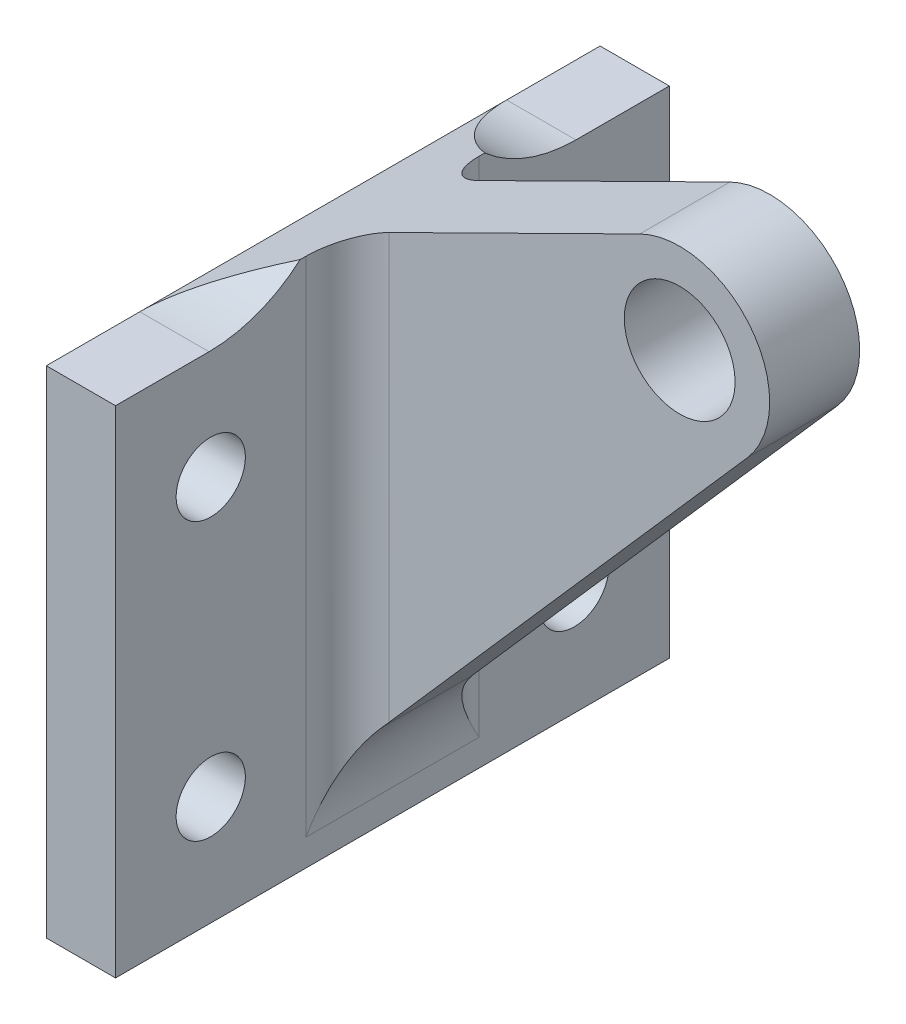
SolidWorks part; units mm, degrees
ref_plane "Front Plane" through (0, 0, 0) normal (0, 0, 1) x (1, 0, 0)
ref_plane "Top Plane" through (0, 0, 0) normal (0, 1, 0) x (1, 0, 0)
ref_plane "Right Plane" through (0, 0, 0) normal (1, 0, 0) x (0, 0, -1)
sketch "Sketch1" plane through (0, 0, 0) normal (0, 0, 1) x (1, 0, 0)
  line L0 (0, 0) -> (39, 35) construction
  line L1 (39, 35) -> (39, 0) construction
  line L2 (39, 0) -> (0, 0) construction
  line L3 (0, 0) -> (0, 20) construction
  line L4 (0, 20) -> (39, 35) construction
  line L5 (10, 0) -> (10, -7.9) construction
  line L6 (0, 20) -> (10, 20) construction
  line L7 (10, 20) -> (10, 27.9) construction
  line L8 (10, 27.9) -> (10, -7.9)
  line L9 (10, 27.9) -> (36.1168, 40.8256)
  line L10 (10, -7.9) -> (43.8855, 30.7126)
  circle A0 centre (39, 35) radius 6.5 construction
  circle A1 centre (39, 35) radius 6.5
  circle A2 centre (39, 35) radius 4
  point P3 (10, 0)
  dimension "D5" = 13
  dimension "D9" = 8
  dimension "D1" = 20
  dimension "D2" = 10
  dimension "D3" = 39
  dimension "D4" = 35
  dimension "D6" = 7.9
  dimension "D7" = 7.9
  dimension "D8" = 10
extrude "Boss-Extrude1" add sketch "Sketch1" along normal mid plane 6.5 contours A1 | A1 L9 L8 L10 region at (21.6634, 19.1269, 0) region at (42.3315, 40.3661, 0)
sketch "Sketch3" plane through (10, 0, 0) normal (-1, 0, 0) x (0, 0, 1)
  line L0 (3.25, -7.9) -> (-3.25, -7.9) construction
  line L1 (-20, 27.9) -> (20, 27.9)
  line L2 (-20, 27.9) -> (-20, -7.9)
  line L3 (-20, -7.9) -> (20, -7.9)
  line L4 (20, 27.9) -> (20, -7.9)
  line L5 (3.25, 27.9) -> (-3.25, 27.9) construction
  point P8 (0, 0)
  point P9 (0, -7.9)
  dimension "D1" = 40
extrude "Boss-Extrude3" add sketch "Sketch3" against normal blind 5
fillet "Fillet1" radius 10 3 edges at (15, -2.2025, 0) (12.5, 27.9, -3.25) (12.5, 27.9, 3.25)
fillet "Fillet2" radius 3 2 edges at (15, 12.2032, -3.25) (15, 12.2032, 3.25)
sketch "Sketch5" plane through (10, 0, 0) normal (-1, 0, 0) x (0, 0, 1)
  line L0 (0, 27.9) -> (0, -7.9) construction
  line L1 (13.25, 27.9) -> (-13.25, 27.9) construction
  line L2 (20, -7.9) -> (-20, -7.9) construction
  line L3 (3.25, 37.1442) -> (3.25, -7.9) construction
  line L4 (13.125, -7.9) -> (13.125, 0) construction
  line L5 (13.125, 0) -> (13.125, 20) construction
  line L6 (3.25, 31.8593) -> (3.25, 40.8256) construction
  line L7 (6.25, 27.9) -> (6.25, -7.9) construction
  line L8 (6.25, -7.9) -> (20, -7.9) construction
  circle A0 centre (13.125, 0) radius 2.5
  circle A1 centre (13.125, 20) radius 2.5
  point P18 (13.125, -7.9)
  dimension "D3" = 5
  dimension "D4" = 5
  dimension "D1" = 7.9
  dimension "D2" = 20
  dimension "D5" = 3
extrude "Cut-Extrude1" cut sketch "Sketch5" against normal through all
mirror "Mirror1" about plane through (0, 0, 0) normal (0, 0, 1) of "Cut-Extrude1"
